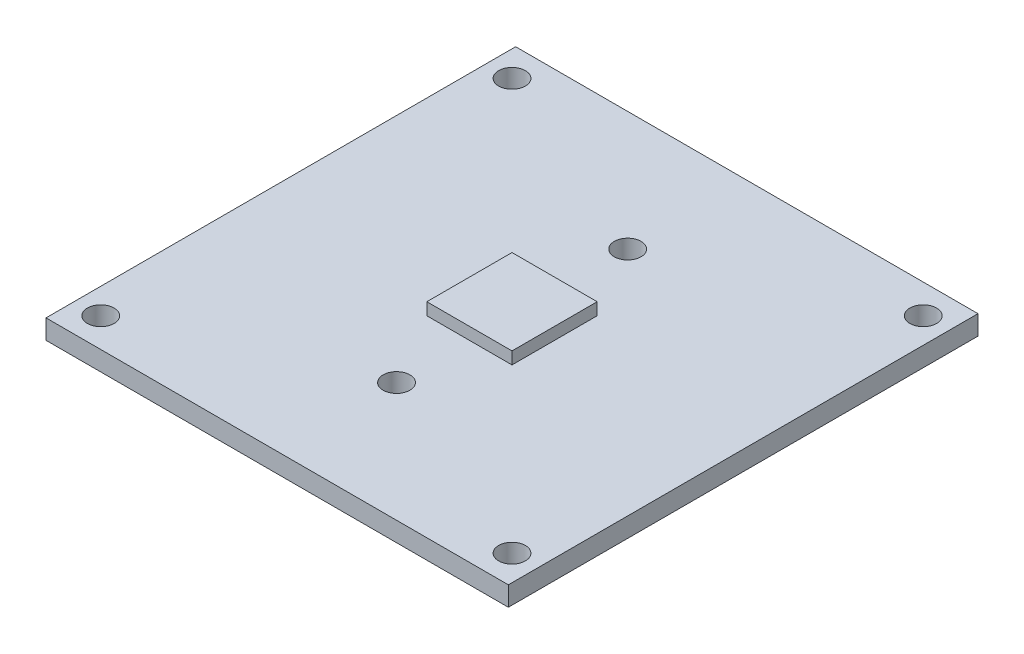
SolidWorks part; units mm, degrees
ref_plane "Front Plane" through (0, 0, 0) normal (0, 0, 1) x (1, 0, 0)
ref_plane "Top Plane" through (0, 0, 0) normal (0, 1, 0) x (1, 0, 0)
ref_plane "Right Plane" through (0, 0, 0) normal (1, 0, 0) x (0, 0, -1)
sketch "Sketch1" plane through (0, 0, 0) normal (0, 1, 0) x (1, 0, 0)
  line L0 (-7.4919, 7.6) -> (-1.9919, 7.6)
  line L1 (-19, -19.3) -> (19, -19.3)
  line L2 (-19, -19.3) -> (-19, 19.3)
  line L3 (-19, 19.3) -> (19, 19.3)
  line L4 (19, -19.3) -> (19, 19.3)
  line L5 (-19, -19.3) -> (19, 19.3) construction
  line L6 (-19, 19.3) -> (19, -19.3) construction
  line L7 (2.0081, 9.5) -> (2.0081, 7.6)
  line L8 (-1.9919, 7.6) -> (-1.9919, 9.5)
  line L9 (-1.9919, -7.6) -> (-7.4919, -7.6)
  line L10 (-1.9919, -9.5) -> (-1.9919, -7.6)
  line L11 (2.0081, -7.6) -> (2.0081, -9.5)
  line L12 (7.5081, -7.6) -> (2.0081, -7.6)
  line L13 (7.5081, 7.6) -> (7.5081, -7.6)
  line L14 (2.0081, 7.6) -> (7.5081, 7.6)
  line L15 (-7.4919, -7.6) -> (-7.4919, 7.6)
  line L16 (-19, 0) -> (19, 0) construction
  line L17 (0, 19.3) -> (0, -19.3) construction
  line L19 (-16, -14.3) -> (16, -14.3)
  line L20 (-16, -14.3) -> (-16, 14.3)
  line L21 (-16, 14.3) -> (16, 14.3)
  line L22 (16, -14.3) -> (16, 14.3)
  line L23 (-16, -14.3) -> (16, 14.3) construction
  line L24 (-16, 14.3) -> (16, -14.3) construction
  line L25 (-3.5, -3.5) -> (3.5, -3.5)
  line L26 (-3.5, -3.5) -> (-3.5, 3.5)
  line L27 (-3.5, 3.5) -> (3.5, 3.5)
  line L28 (3.5, -3.5) -> (3.5, 3.5)
  line L29 (-3.5, -3.5) -> (3.5, 3.5) construction
  line L30 (-3.5, 3.5) -> (3.5, -3.5) construction
  arc A0 (2.0081, 9.5) -> (-1.9919, 9.5) centre (0.0081, 9.5) ccw
  arc A3 (-1.9919, -9.5) -> (2.0081, -9.5) centre (0.0081, -9.5) ccw
  circle A6 centre (0.0081, 9.5) radius 1.1
  circle A7 centre (0.0081, -9.5) radius 1.1
  circle A8 centre (-16.9, 16.9) radius 1.1
  circle A9 centre (16.9, 16.9) radius 1.1
  circle A10 centre (16.9, -16.9) radius 1.1
  circle A11 centre (-16.9, -16.9) radius 1.1
  point P0 (0, 0)
  point P34 (7.5081, 0)
  point P35 (-7.4919, 0)
  point P36 (0, 0)
  point P41 (0, 0)
  point P46 (0, 0)
  dimension "D3" = 2.2
  dimension "D6" = 2
  dimension "D7" = 2.2
  dimension "D8" = 2.4
  dimension "D9" = 2.1
  dimension "D1" = 38.6
  dimension "D2" = 38
  dimension "D4" = 15.2
  dimension "D5" = 15
  dimension "D10" = 11.5081
  dimension "D11" = 5.5
  dimension "D12" = 4
  dimension "D13" = 19
  dimension "D14" = 3
  dimension "D15" = 5
  dimension "D16" = 7
extrude "Boss-Extrude1" add sketch "Sketch1" along normal blind 1.6 contours L1 L4 L3 L2 A9 A8 L22 L19 L20 L21 A10 A11 | L19 L22 L21 L20 A3 L10 L9 L15 L0 L8 A0 L7 L14 L13 L12 L11 | L10 A3 L11 L12 L13 L14 L7 A0 L8 L0 L15 L9 A6 A7 | L25 L28 L27 L26 region at (-4.7419, 0, -7.3254) region at (-18.4583, 0, 0) region at (-15.5708, 0, 0) region at (0, 0, 0)
extrude "Boss-Extrude2" add sketch "Sketch1<3>" against normal blind 2.3 contours L19 L22 L21 L20 A3 L10 L9 L15 L0 L8 A0 L7 L14 L13 L12 L11 | L10 A3 L11 L12 L13 L14 L7 A0 L8 L0 L15 L9 A6 A7 | L25 L28 L27 L26 region at (-4.7419, 0, -7.3254) region at (-15.5708, 0, 0) region at (0, 0, 0)
sketch "Sketch1<3>" plane through (0, 0, 0) normal (0, 1, 0) x (1, 0, 0) same geometry as "Sketch1"
ref_plane "Plane1" through (0, 1.6, 0) normal (0, 1, 0) x (1, 0, 0)
sketch "Sketch2" plane through (0, 1.6, 0) normal (0, 1, 0) x (1, 0, 0)
  line L1 (-3.5, -3.5) -> (3.5, -3.5)
  line L2 (-3.5, -3.5) -> (-3.5, 3.5)
  line L3 (-3.5, 3.5) -> (3.5, 3.5)
  line L4 (3.5, -3.5) -> (3.5, 3.5)
  line L5 (-3.5, -3.5) -> (3.5, 3.5) construction
  line L6 (-3.5, 3.5) -> (3.5, -3.5) construction
  point P0 (0, 0)
extrude "Boss-Extrude4" add sketch "Sketch2" along normal blind 1
